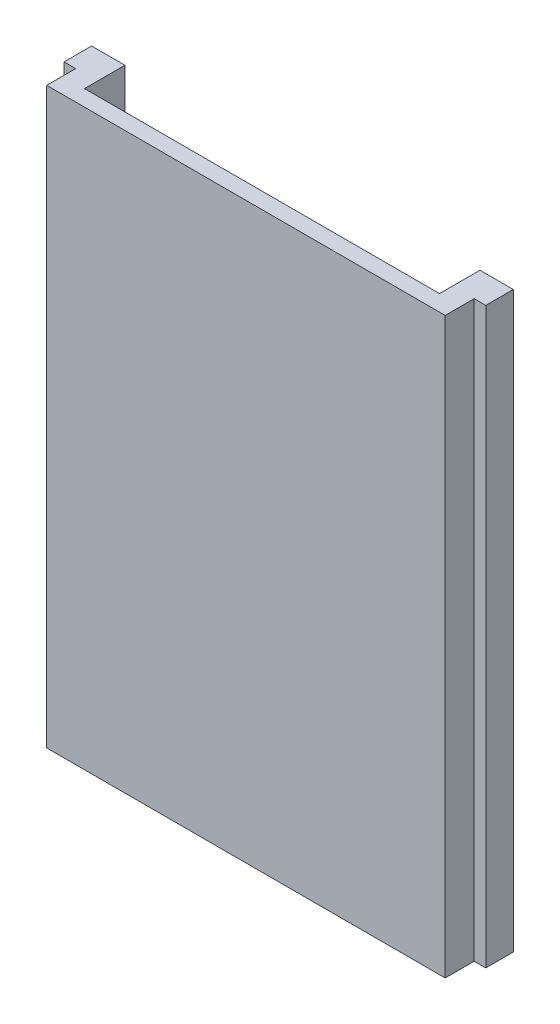
SolidWorks part; units mm, degrees
ref_plane "Alzado" through (0, 0, 0) normal (0, 0, 1) x (1, 0, 0)
ref_plane "Planta" through (0, 0, 0) normal (0, 1, 0) x (1, 0, 0)
ref_plane "Vista lateral" through (0, 0, 0) normal (1, 0, 0) x (0, 0, -1)
sketch "Croquis1" plane through (0, 0, 0) normal (0, 1, 0) x (1, 0, 0)
  line L5 (-4, 10) -> (-4, 19.5)
  line L14 (7.5, 19.5) -> (7.5, 5.5361)
  line L17 (-4, 19.5) -> (7.5, 19.5)
  line L19 (0, 0) -> (137.5, 0)
  line L20 (0, 0) -> (0, 10)
  line L21 (0, 10) -> (-4, 10)
  line L23 (7.5, 5.5361) -> (130, 5.5361)
  line L25 (68.75, 54.2093) -> (68.75, -41.2998) construction
  line L26 (137.5, 10) -> (141.5, 10)
  line L27 (137.5, 0) -> (137.5, 10)
  line L28 (141.5, 19.5) -> (130, 19.5)
  line L29 (130, 19.5) -> (130, 5.5361)
  line L30 (141.5, 10) -> (141.5, 19.5)
  point P3 (68.75, 5.5361)
  point P12 (68.75, 0)
  dimension "D1" = 68.75
  dimension "D2" = 10
  dimension "D3" = 9.5
  dimension "D4" = 11.5
  dimension "D5" = 72.75
  dimension "D7" = 5.5361
extrude "Saliente-Extruir4" add sketch "Croquis1" along normal blind 198 contours L17 L14 L23 L29 L28 L30 L26 L27 L19 L20 L21 L5
ref_plane "Plano1" through (68.75, 0, 0) normal (1, 0, 0) x (0, 0, -1)
